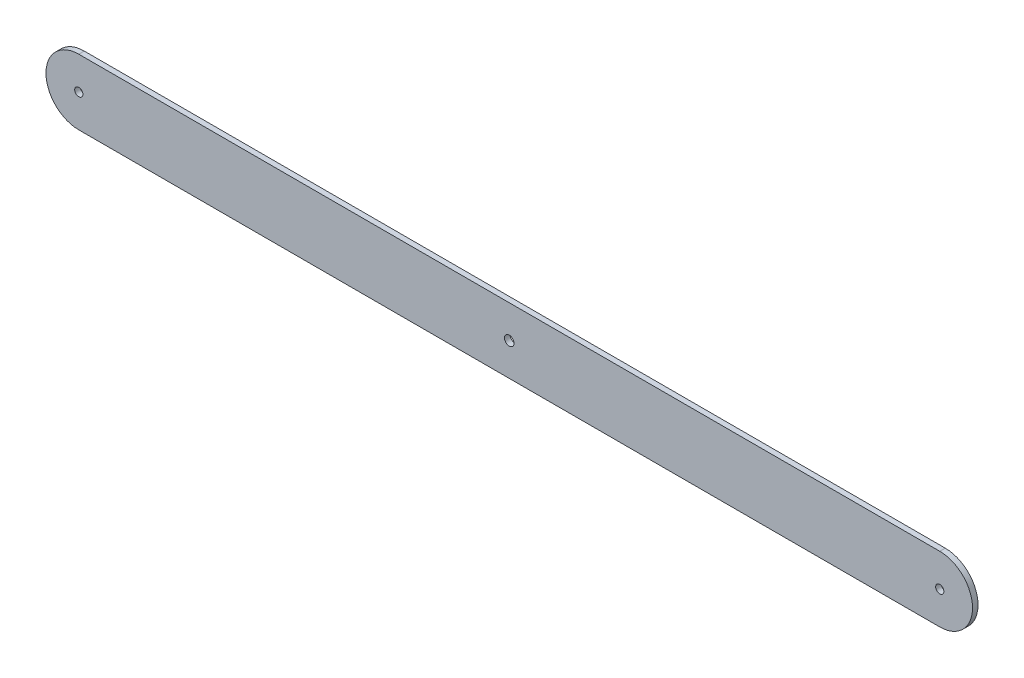
SolidWorks part; units mm, degrees
ref_plane "Front Plane" through (0, 0, 0) normal (0, 0, 1) x (1, 0, 0)
ref_plane "Top Plane" through (0, 0, 0) normal (0, 1, 0) x (1, 0, 0)
ref_plane "Right Plane" through (0, 0, 0) normal (1, 0, 0) x (0, 0, -1)
ref_axis "X" through (-88.99, 0, 0) along (1, 0, 0)
ref_axis "Y" through (0, 55, 0) along (0, -1, 0)
ref_axis "Z" through (0, 0, -88.99) along (0, 0, 1)
sketch "Sketch1" plane through (0, 0, 0) normal (0, 0, 1) x (1, 0, 0)
  line L0 (-157.6, 0) -> (157.6, 0) construction
  line L1 (-157.6, 12) -> (157.6, 12)
  line L2 (-157.6, -12) -> (157.6, -12)
  line L4 (-32.5, 12) -> (32.5, 12) construction
  arc A0 (-157.6, 12) -> (-157.6, -12) centre (-157.6, 0) ccw
  arc A1 (157.6, -12) -> (157.6, 12) centre (157.6, 0) ccw
  circle A2 centre (-157.6, 0) radius 1.5
  circle A3 centre (0, 0) radius 1.75
  circle A4 centre (157.6, 0) radius 1.5
  circle A5 centre (-157.6, 0) radius 1.5 construction
  circle A6 centre (0, 0) radius 1.75 construction
  point P2 (0, 0)
extrude "Boss-Extrude1" add sketch "Sketch1" along normal blind 2
